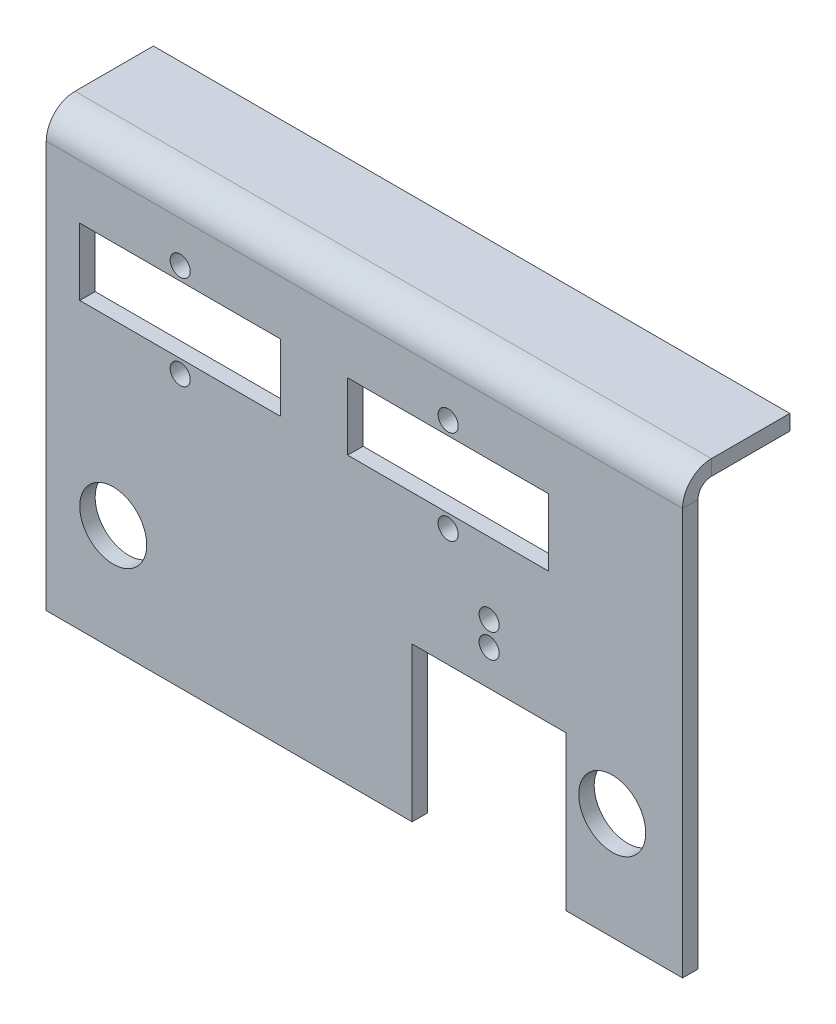
SolidWorks part; units mm, degrees
note: The reader was unsure of these and kept them because the rebuilt part matched: flange length of "Edge-Flange1".
ref_plane "Front Plane" through (0, 0, 0) normal (0, 0, 1) x (1, 0, 0)
ref_plane "Top Plane" through (0, 0, 0) normal (0, 1, 0) x (1, 0, 0)
ref_plane "Right Plane" through (0, 0, 0) normal (1, 0, 0) x (0, 0, -1)
sketch "Sketch1" plane through (0, 0, 0) normal (0, 0, 1) x (1, 0, 0)
  line L1 (0, 0) -> (95, 0)
  line L2 (0, 0) -> (0, 65)
  line L3 (0, 65) -> (95, 65)
  line L4 (95, 0) -> (95, 65)
  line L5 (0, 0) -> (95, 65) construction
  line L6 (0, 65) -> (95, 0) construction
  point P4 (47.5, 32.5)
  dimension "D1" = 65
  dimension "D2" = 95
base flange "Base-Flange1" sketch "Sketch1" thickness 2.3 reverse thickness direction no parameters "D1"=2
edge flange "Edge-Flange1" sketch "Sketch8" flange angle 90 flange length 16 flange position material inside bend radius 2 thickness 2.3 relief rectangular parameters "D6"=10
sketch "Sketch8" plane through (0, 65, -2.3) normal (0, -1, 0) x (-1, 0, 0)
  line L2 (-95, 0) -> (-95, 13.7)
  line L3 (-95, 13.7) -> (0, 13.7)
  line L4 (0, 13.7) -> (0, 0)
  line L5 (0, 0) -> (-95, 0) construction
  line L6 (0, 0) -> (-95, 0)
bend "EdgeBend1" bend radius 2 bend angle 90 parameters "D5"=1
sketch "Sketch9" plane through (0, 0, 0) normal (0, 0, 1) x (1, 0, 0)
  line L0 (0, 0) -> (95, 0) construction
  line L1 (54.62, 0) -> (77.62, 0)
  line L2 (54.62, 0) -> (54.62, 23)
  line L3 (54.62, 23) -> (77.62, 23)
  line L4 (77.62, 0) -> (77.62, 23)
  line L5 (54.62, 0) -> (77.62, 23) construction
  line L6 (54.62, 23) -> (77.62, 0) construction
  line L7 (0, 60.7) -> (0, 0) construction
  circle A0 centre (66.12, 28.3) radius 1.5
  circle A1 centre (66.12, 31.9) radius 1.5
  point P4 (66.12, 11.5)
  dimension "D6" = 3
  dimension "D7" = 3
  dimension "D1" = 23
  dimension "D2" = 23
  dimension "D3" = 54.62
  dimension "D4" = 5.3
  dimension "D5" = 31.9
extrude "Cut-Extrude1" cut sketch "Sketch9" against normal up to next normal cut yes
sketch "Sketch10" plane through (0, 0, -2.3) normal (0, 0, -1) x (-1, 0, 0)
  line L0 (-35, 52.6) -> (-5, 52.6)
  line L1 (-35, 52.6) -> (-35, 42.6)
  line L2 (-35, 42.6) -> (-5, 42.6)
  line L3 (-5, 52.6) -> (-5, 42.6)
  line L4 (-35, 52.6) -> (-5, 42.6) construction
  line L5 (-35, 42.6) -> (-5, 52.6) construction
  line L6 (-75, 52.6) -> (-45, 52.6)
  line L7 (-75, 52.6) -> (-75, 42.6)
  line L8 (-75, 42.6) -> (-45, 42.6)
  line L9 (-45, 52.6) -> (-45, 42.6)
  line L10 (-75, 52.6) -> (-45, 42.6) construction
  line L11 (-75, 42.6) -> (-45, 52.6) construction
  line L12 (0, 60.7) -> (0, 0) construction
  line L13 (0, 0) -> (-54.62, 0) construction
  circle A0 centre (-60, 54.6) radius 1.5
  circle A1 centre (-60, 40.6) radius 1.5
  circle A2 centre (-20, 54.6) radius 1.5
  circle A3 centre (-20, 40.6) radius 1.5
  point P4 (-20, 47.6)
  point P9 (-60, 47.6)
  dimension "D1" = 30
  dimension "D2" = 30
  dimension "D3" = 10
  dimension "D4" = 7
  dimension "D5" = 7
  dimension "D6" = 7
  dimension "D7" = 7
  dimension "D8" = 10
  dimension "D9" = 10
  dimension "D10" = 5
  dimension "D11" = 47.6
  dimension "D12" = 47.6
extrude "Cut-Extrude3" cut sketch "Sketch10" against normal up to next normal cut yes
sketch "Sketch11" plane through (0, 0, -2.3) normal (0, 0, -1) x (-1, 0, 0)
  line L2 (-77.62, 0) -> (-95, 0) construction
  line L3 (0, 60.7) -> (0, 0) construction
  line L5 (0, 0) -> (-54.62, 0) construction
  circle A0 centre (-10, 16) radius 5
  circle A1 centre (-84.5, 16) radius 5
  dimension "D3" = 10
  dimension "D5" = 10
  dimension "D1" = 10
  dimension "D2" = 16
  dimension "D4" = 74.5
  dimension "D6" = 16
extrude "Cut-Extrude4" cut sketch "Sketch11" against normal up to next normal cut yes
sketch "Bend-Lines1" [suppressed] plane through (0, 0, 0) normal (0, 1, 0) x (1, 0, 0)
sketch "Bounding-Box1" [suppressed] plane through (0, 0, 0) normal (0, 1, 0) x (1, 0, 0)
sheet metal parameters "Sheet-Metal1" thickness 2.3 parameters "D1"=2
flat pattern "Flat-Pattern1" [suppressed]
sketch "Bend-Lines2" plane through (0, 0, 0) normal (0, 1, 0) x (1, 0, 0)
sketch3d "Bounding-Box2" [suppressed]
  line L0 (0, 0, 0) -> (-90, 0, 0) construction
  line L1 (0, 65, 0) -> (-90, 65, 0) construction
  line L2 (0, 0, 0) -> (0, 65, 0) construction
  line L3 (-90, 0, 0) -> (-90, 65, 0) construction
sheet metal parameters "Sheet-Metal2" thickness 2.3 parameters "D1"=2
flat pattern "Flat-Pattern1"
sketch "Bend-Lines2" plane through (0, 0, 0) normal (0, 0, 1) x (1, 0, 0)
  line L0 (90, 63.174) -> (0, 63.174) construction
  line L1 (90, 63.174) -> (0, 63.174) construction
sketch3d "Bounding-Box2" [suppressed]
  line L0 (0, 0, 0) -> (90, 0, 0) construction
  line L1 (0, 77.348, 0) -> (90, 77.348, 0) construction
  line L2 (0, 0, 0) -> (0, 77.348, 0) construction
  line L3 (90, 0, 0) -> (90, 77.348, 0) construction
bend of the flat pattern "Flatten-<EdgeBend1>1"
sheet metal parameters "Sheet-Metal3" thickness 2.3 parameters "D1"=2
flat pattern "Flat-Pattern1"
sketch "Bend-Lines2" plane through (0, 0, 0) normal (0, 0, 1) x (1, 0, 0)
  line L0 (90, 63.174) -> (0, 63.174) construction
  line L1 (90, 63.174) -> (0, 63.174) construction
sketch3d "Bounding-Box2" [suppressed]
  line L0 (0, 0, 0) -> (90, 0, 0) construction
  line L1 (0, 77.348, 0) -> (90, 77.348, 0) construction
  line L2 (0, 0, 0) -> (0, 77.348, 0) construction
  line L3 (90, 0, 0) -> (90, 77.348, 0) construction
bend of the flat pattern "Flatten-<EdgeBend1>1"
sheet metal parameters "Sheet-Metal5" thickness 2.3 parameters "D1"=2
flat pattern "Flat-Pattern1"
sketch "Bend-Lines2" plane through (0, 0, 0) normal (0, 0, 1) x (1, 0, 0)
  line L0 (90, 63.174) -> (0, 63.174) construction
  line L1 (90, 63.174) -> (0, 63.174) construction
sketch3d "Bounding-Box2" [suppressed]
  line L0 (0, 0, 0) -> (90, 0, 0) construction
  line L1 (0, 77.348, 0) -> (90, 77.348, 0) construction
  line L2 (0, 0, 0) -> (0, 77.348, 0) construction
  line L3 (90, 0, 0) -> (90, 77.348, 0) construction
bend of the flat pattern "Flatten-<EdgeBend1>1"
sheet metal parameters "Sheet-Metal6" thickness 2.3 parameters "D1"=2
flat pattern "Flat-Pattern1"
sketch "Bend-Lines2" plane through (0, 0, 0) normal (0, 0, 1) x (1, 0, 0)
  line L0 (95, 63.174) -> (0, 63.174) construction
  line L1 (95, 63.174) -> (0, 63.174) construction
sketch3d "Bounding-Box2" [suppressed]
  line L0 (0, 0, 0) -> (95, 0, 0) construction
  line L1 (0, 77.348, 0) -> (95, 77.348, 0) construction
  line L2 (0, 0, 0) -> (0, 77.348, 0) construction
  line L3 (95, 0, 0) -> (95, 77.348, 0) construction
bend of the flat pattern "Flatten-<EdgeBend1>1"
